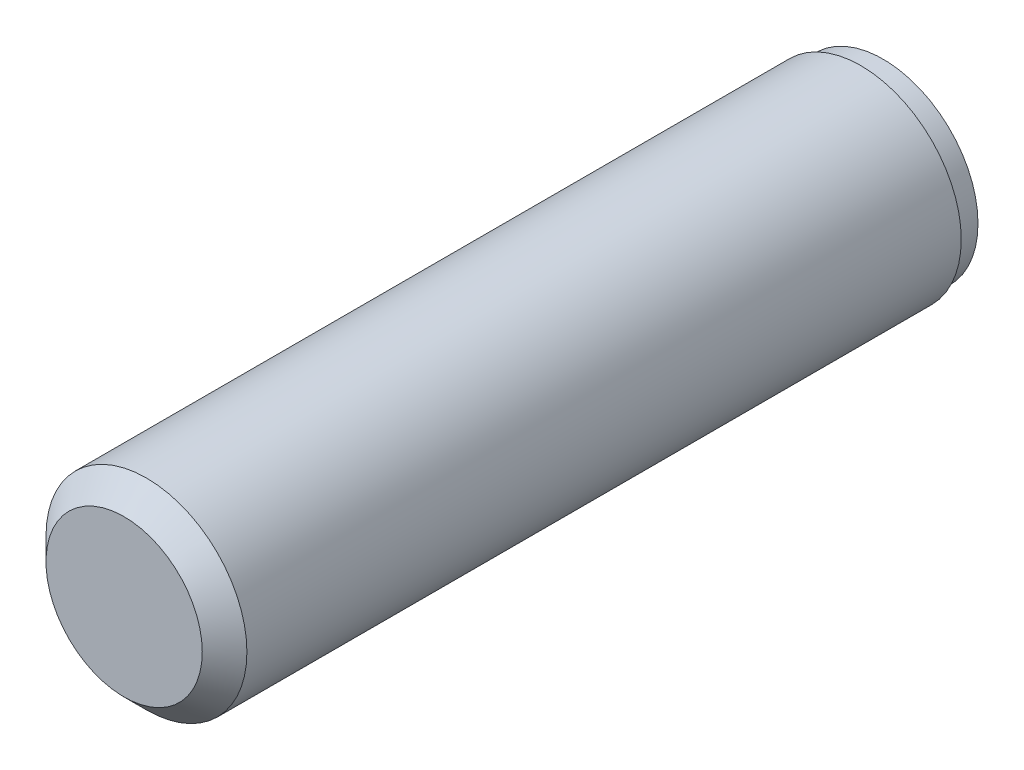
SolidWorks part; units mm, degrees
material "PMMA"
ref_plane "Front Plane" through (0, 0, 0) normal (0, 0, 1) x (1, 0, 0)
ref_plane "Top Plane" through (0, 0, 0) normal (0, 1, 0) x (1, 0, 0)
ref_plane "Right Plane" through (0, 0, 0) normal (1, 0, 0) x (0, 0, -1)
sketch "Sketch1" plane through (0, 0, 0) normal (0, 0, 1) x (1, 0, 0)
  circle A0 centre (0, 0) radius 9
  dimension "D1" = 18
extrude "Boss-Extrude1" add sketch "Sketch1" along normal blind 66
cosmetic thread "Cosmetic Thread1" parameters "D1"=45, "D2"=15.294
sketch "Sketch2" plane through (0, 0, 0) normal (0, 0, -1) x (-1, 0, 0)
  circle A0 centre (0, 0) radius 8.5
  dimension "D1" = 17
extrude "Boss-Extrude2" add sketch "Sketch2" along normal blind 2
sketch "Sketch3" plane through (0, 0, -2) normal (0, 0, -1) x (-1, 0, 0)
  circle A0 centre (0, 0) radius 8
  dimension "D1" = 16
extrude "Cut-Extrude1" cut sketch "Sketch3" against normal blind 1.5
sketch "Sketch4" plane through (0, 0, -0.5) normal (0, 0, -1) x (-1, 0, 0)
  line L0 (0, 9.6629) -> (0, -10.1157) construction
  circle A0 centre (0, 4) radius 3
  circle A1 centre (0, -4) radius 3
  dimension "D1" = 6
  dimension "D2" = 6
  dimension "D3" = 4
  dimension "D4" = 4
extrude "Boss-Extrude3" add sketch "Sketch4" along normal blind 1
fillet "Fillet1" radius 1 2 edges at (-3, -4, -1.5) (-3, 4, -1.5)
chamfer "Chamfer1" distance 2 angle 45 1 edges at (9, 0, 66)
